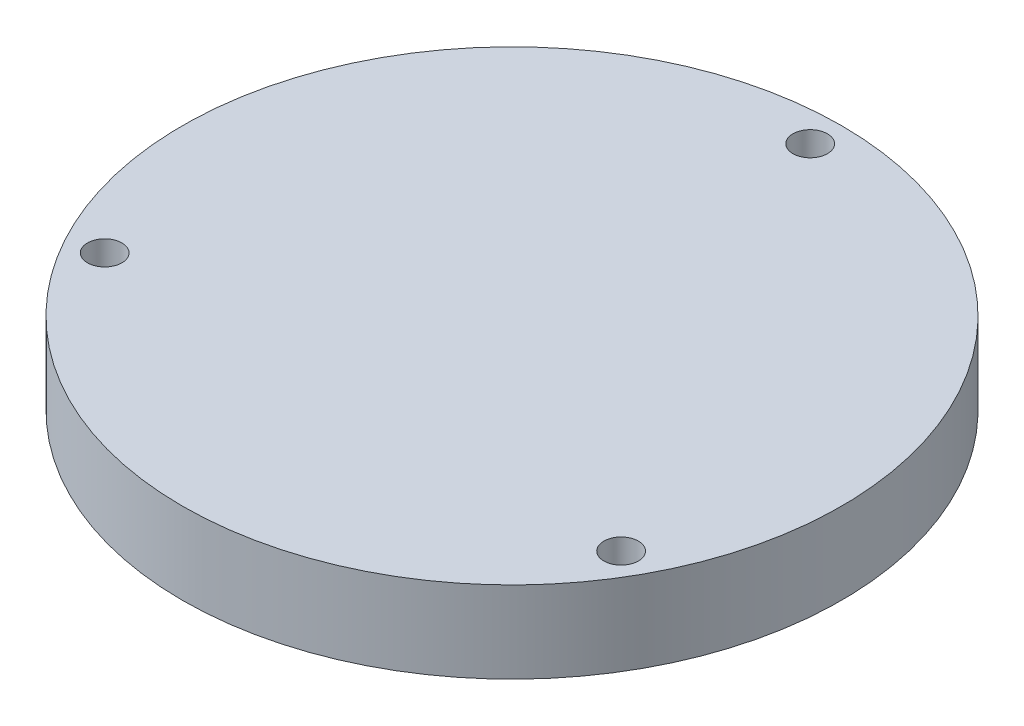
SolidWorks part; units mm, degrees
ref_plane "Plan de face" through (0, 0, 0) normal (0, 0, 1) x (1, 0, 0)
ref_plane "Plan de dessus" through (0, 0, 0) normal (0, 1, 0) x (1, 0, 0)
ref_plane "Plan de droite" through (0, 0, 0) normal (1, 0, 0) x (0, 0, -1)
sketch "Esquisse1" plane through (0, 0, 0) normal (0, 1, 0) x (1, 0, 0)
  line L0 (0, 55.0784) -> (0, -55.7052) construction
  line L1 (-4, 47.5) -> (-4, 50.3413) construction
  line L2 (4, 47.5) -> (4, 50.3413) construction
  line L3 (0, 0) -> (68.6571, 39.6392) construction
  line L4 (0, 0) -> (-63.5298, 36.6789) construction
  line L5 (-4, 48.1274) -> (-4, 47.5)
  line L6 (4, 48.1274) -> (4, 47.5)
  line L7 (43.6796, -20.5996) -> (43.1362, -20.2859)
  line L8 (39.6796, -27.5278) -> (39.1362, -27.2141)
  line L9 (-39.6796, -27.5278) -> (-39.1362, -27.2141)
  line L10 (-43.6796, -20.5996) -> (-43.1362, -20.2859)
  circle A0 centre (0, 0) radius 52.5
  circle A1 centre (0, 0) radius 50.5 construction
  circle A2 centre (0, 47.5) radius 4
  arc A3 (6.2474, 50.1121) -> (43.7343, 25.25) centre (0, 0) cw
  arc A4 (-6.2474, 50.1121) -> (-43.7343, 25.25) centre (0, 0) ccw
  arc A5 (4, 48.1274) -> (6.2474, 50.1121) centre (6, 48.1274) cw
  arc A6 (-4, 48.1274) -> (-6.2474, 50.1121) centre (-6, 48.1274) ccw
  arc A7 (46.522, -19.6456) -> (43.7343, 25.25) centre (0, 0) ccw
  circle A8 centre (41.1362, -23.75) radius 4
  arc A9 (40.2746, -30.4665) -> (0, -50.5) centre (0, 0) cw
  arc A10 (39.6796, -27.5278) -> (40.2746, -30.4665) centre (38.6796, -29.2599) cw
  arc A11 (43.6796, -20.5996) -> (46.522, -19.6456) centre (44.6796, -18.8676) ccw
  arc A12 (-40.2746, -30.4665) -> (0, -50.5) centre (0, 0) ccw
  circle A13 centre (-41.1362, -23.75) radius 4
  arc A14 (-46.522, -19.6456) -> (-43.7343, 25.25) centre (0, 0) cw
  arc A15 (-43.6796, -20.5996) -> (-46.522, -19.6456) centre (-44.6796, -18.8676) cw
  arc A16 (-39.6796, -27.5278) -> (-40.2746, -30.4665) centre (-38.6796, -29.2599) ccw
  point P49 (0, 0)
  dimension "D1" = 105
  dimension "D2" = 2
  dimension "D3" = 2
  dimension "D4" = 8
  dimension "D5" = 47.5
  dimension "D6" = 60
  dimension "D7" = 60
  dimension "D8" = 3
extrude "Boss.-Extru.1" add sketch "Esquisse1" along normal blind 10 contours A0 A16 L9 A13 L10 A15 A14 A4 A6 L5 A2 L6 A5 A3 A7 A11 L7 A8 L8 A10 A9 A12 | A13 | A8 | A2 A9 region at (0, 0, -47.5) region at (-41.1362, 0, 23.75) region at (41.1362, 0, 23.75) region at (-51.0151, 0, 0)
sketch "Esquisse2" plane through (0, 10, 0) normal (0, 1, 0) x (1, 0, 0)
  circle A1 centre (0, 0) radius 52.5
  circle A2 centre (0, 0) radius 52.5
  dimension "D1" = 0
extrude "Boss.-Extru.2" add sketch "Esquisse2" along normal blind 3
sketch "Esquisse3" plane through (0, 0, 0) normal (0, -1, 0) x (1, 0, 0)
  circle A0 centre (0, -47.5) radius 2.75
  circle A1 centre (0, 0) radius 52.5
  circle A2 centre (0, 0) radius 52.5
  circle A3 centre (-41.1362, 23.75) radius 2.75
  circle A4 centre (41.1362, 23.75) radius 2.75
  point P13 (0, 0)
  dimension "D2" = 5.5
  dimension "D1" = 0
  dimension "D3" = 3
extrude "Enlèv. mat.-Extru.2" cut sketch "Esquisse3" against normal through all from offset 3 contours A4 | A3 | A0 offset against normal yes
sketch "Esquisse4" plane through (0, 0, 0) normal (0, -1, 0) x (1, 0, 0)
  arc A0 (4, -47.5) -> (-4, -47.5) centre (0, -47.5) ccw construction
  arc A1 (4, -47.5) -> (-4, -47.5) centre (0, -47.5) ccw
  circle A2 centre (0, -47.5) radius 1.55
  circle A3 centre (-41.1362, 23.75) radius 1.55
  circle A4 centre (41.1362, 23.75) radius 1.55
  point P11 (0, 0)
  dimension "D1" = 3
  dimension "D2" = 3.1
extrude "Enlèv. mat.-Extru.3" cut sketch "Esquisse4" against normal through all contours A2 | A3 | A4 region at (0, 0, -47.5) region at (-41.1362, 0, 23.75) region at (41.1362, 0, 23.75)
sketch "Esquisse5" plane through (0, 13, 0) normal (0, 1, 0) x (1, 0, 0)
  line L0 (-57.8947, 998.3227) -> (0, 0)
  line L1 (0, 0) -> (57.8947, 998.3227)
  line L2 (-57.8947, 998.3227) -> (57.8947, 998.3227)
  line L3 (893.5202, -449.023) -> (835.6254, -549.2997)
  line L4 (0, 0) -> (835.6254, -549.2997)
  line L5 (893.5202, -449.023) -> (0, 0)
  line L6 (-835.6254, -549.2997) -> (-893.5202, -449.023)
  line L7 (0, 0) -> (-893.5202, -449.023)
  line L8 (-835.6254, -549.2997) -> (0, 0)
  circle A0 centre (0, 0) radius 1000 construction
  circle A1 centre (0, 47.5) radius 2.75 construction
  circle A2 centre (0, 0) radius 52.5
  circle A3 centre (0, 0) radius 52.5
  circle A4 centre (0, 47.5) radius 2.75 construction
  point P19 (0, 0)
  dimension "D1" = 0
  dimension "D2" = 2000
  dimension "D3" = 115.7895
  dimension "D4" = 3
